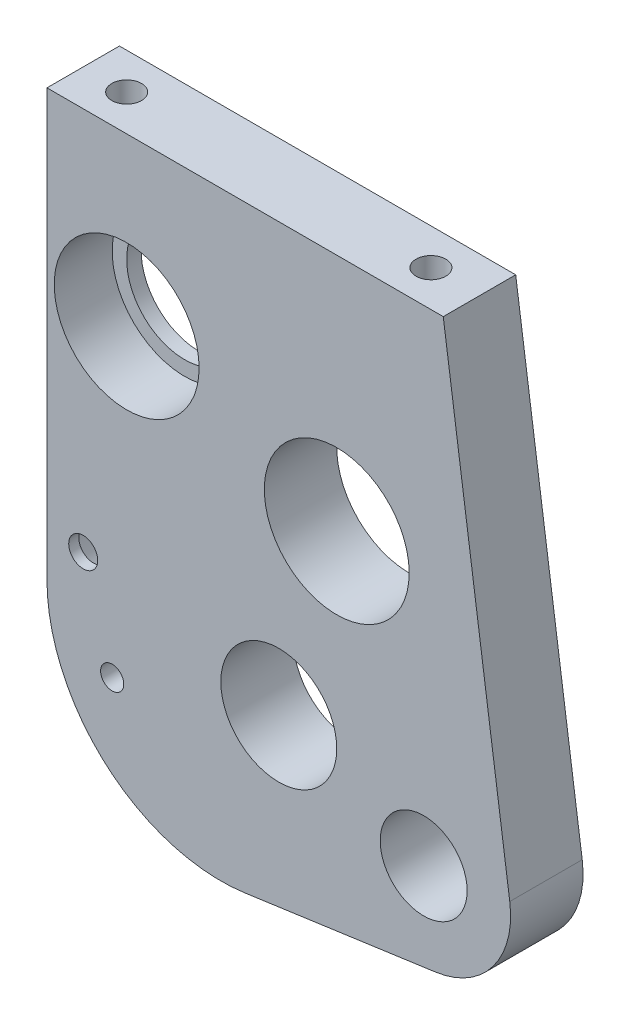
SolidWorks part; units mm, degrees
material "45"
ref_plane "前视基准面" through (0, 0, 0) normal (0, 0, 1) x (1, 0, 0)
ref_plane "上视基准面" through (0, 0, 0) normal (0, 1, 0) x (1, 0, 0)
ref_plane "右视基准面" through (0, 0, 0) normal (1, 0, 0) x (0, 0, -1)
sketch "草图1" plane through (0, 0, 0) normal (0, 0, 1) x (1, 0, 0)
  line L1 (0, 0) -> (34, 0)
  line L2 (0, 0) -> (0, -38.5)
  line L3 (0, -38.5) -> (34, -38.5)
  line L4 (34, 0) -> (34, -38.5)
  dimension "D1" = 34
  dimension "D2" = 38.5
  dimension "D3" = 90
extrude "拉伸1" add sketch "草图1" along normal blind 5
fillet "圆角1" radius 12 1 edges at (0, -38.5, 2.5)
sketch "草图2" plane through (0, 0, 5) normal (0, 0, 1) x (1, 0, 0)
  line L0 (0, 0) -> (0, -26.5) construction
  line L1 (34, 0) -> (0, 0) construction
  circle A0 centre (26, -32.5) radius 3
  dimension "D2" = 32.5
  dimension "D3" = 6
  dimension "D1" = 26
extrude "拉伸2" cut sketch "草图2" against normal up to surface (5 mm away) up to face at (15.5029, -21.1971, 0)
sketch "草图3" plane through (0, 0, 5) normal (0, 0, 1) x (1, 0, 0)
  line L0 (0, 0) -> (0, -26.5) construction
  line L1 (34, 0) -> (0, 0) construction
  circle A0 centre (5.5, -10.5) radius 4
  dimension "D1" = 5.5
  dimension "D2" = 10.5
  dimension "D3" = 8
extrude "拉伸3" cut sketch "草图3" against normal up to surface (5 mm away) up to face at (29, -32.5, 0)
sketch "草图4" plane through (0, 0, 5) normal (0, 0, 1) x (1, 0, 0)
  circle A0 centre (5.5, -10.5) radius 5
  dimension "D1" = 10
extrude "拉伸4" cut sketch "草图4" against normal blind 4
sketch "草图5" plane through (0, 0, 0) normal (0, 1, 0) x (1, 0, 0)
  line L0 (3, -2.5) -> (24, -2.5)
  line L1 (34, 0) -> (0, 0) construction
  line L2 (17, 0) -> (17, -2.5) construction
  line L3 (0, -5) -> (0, 0) construction
  dimension "D1" = 2.5
  dimension "D2" = 21
  dimension "D3" = 3
hole_wizard "M2.5 螺纹孔1" positions "3D草图1" profile "草图6" tap size "M2.5" standard "GB"
sketch3d "3D草图1"
  point P0 (3, 0, 2.5)
  point P3 (24, 0, 2.5)
sketch "草图6" plane through (3, 0, 2.5) normal (1, 0, 0) x (0, 0, 1)
  line L0 (0, 0) -> (0, 7.9659)
  line L1 (0, 7.9659) -> (1.025, 7.35)
  line L2 (1.025, 7.35) -> (1.025, 0)
  line L5 (1.025, 0) -> (0, 0)
  line L10 (0, 7.9659) -> (-1.025, 7.35) construction
  line L11 (0, -6.35) -> (0, 107.95) construction
  dimension "螺纹孔钻头直径" = 2.05
  dimension "螺纹孔钻头深度" = 7.35
  dimension "导头角度" = 118
cosmetic thread "孔螺蚊线1" parameters "D1"=6, "D2"=2.5
cosmetic thread "孔螺蚊线2" parameters "D1"=6, "D2"=2.5
chamfer "倒角1" [suppressed] distance 0.5 angle 45
chamfer "倒角2" [suppressed] distance 0.5 angle 45
sketch "草图7" plane through (0, 0, 0) normal (0, 0, -1) x (-1, 0, 0)
  line L1 (-12, -38.5) -> (-34, -38.5) construction
  line L2 (-31.9416, -31.665) -> (-27.4914, 0)
  line L3 (-34, 0) -> (0, 0) construction
  line L4 (-26, -38.5) -> (-34, -38.5)
  line L5 (-34, -38.5) -> (-34, 0) construction
  line L6 (-34, -38.5) -> (-34, 0)
  line L7 (-34, 0) -> (-27.4914, 0)
  arc A0 (-31.9416, -31.665) -> (-26, -38.5) centre (-26, -32.5) ccw
  circle A1 centre (-26, -32.5) radius 3 construction
  dimension "D1" = 6
  dimension "D2" = 8
extrude "拉伸5" cut sketch "草图7" against normal up to surface (5 mm away) up to face at (10.5, -10.5, 5)
sketch "Sketch1" plane through (0, 0, 0) normal (0, 0, -1) x (-1, 0, 0)
  line L0 (-26.835, -38.4416) -> (-13.6701, -40.2918)
  line L1 (0, 0) -> (0, -26.5) construction
  line L2 (0, -25.5198) -> (0, -28.4086)
  line L3 (-29.4415, -37.4149) -> (0, -25.5198)
  line L4 (-26, -32.5) -> (-29.4415, -37.4149) construction
  line L5 (-12, -38.5) -> (-26, -38.5) construction
  arc A0 (-31.9416, -31.665) -> (-26, -38.5) centre (-26, -32.5) ccw construction
  arc A1 (-29.4415, -37.4149) -> (-26.835, -38.4416) centre (-26, -32.5) ccw
  arc A3 (0, -28.4086) -> (-13.6701, -40.2918) centre (-12, -28.4086) cw
  dimension "D1" = 12
  dimension "D2" = 55
  dimension "D3" = 22
  dimension "D4" = 8
extrude "Extrude1" add sketch "Sketch1" against normal up to surface (5 mm away) up to face at (16.0842, -23.1674, 5)
sketch "草图8" plane through (0, 0, 0) normal (0, 0, -1) x (-1, 0, 0)
  line L1 (0, 0) -> (0, -28.4086) construction
  line L2 (-27.4914, 0) -> (0, 0) construction
  circle A0 centre (-2.5, -25.5) radius 1
  dimension "D3" = 2
  dimension "D1" = 25.5
  dimension "D2" = 2.5
extrude "拉伸6" cut sketch "草图8" against normal up to surface (5 mm away) up to face at (16.439, -23.8299, 5)
sketch "草图9" plane through (0, 0, 0) normal (0, 0, -1) x (-1, 0, 0)
  line L0 (-1.9, -29.2) -> (-6.1, -29.2)
  line L1 (-0.9, -28.2) -> (-0.9, -21)
  line L2 (-7.1, -28.2) -> (-7.1, -21)
  line L3 (-1.9, -20) -> (-6.1, -20)
  line L4 (-2.5, -25.5) -> (-7.596, -25.5) construction
  line L5 (-2.5, -25.5) -> (-2.5, -23.308) construction
  line L6 (-4, -20.9273) -> (-4, -31.0273) construction
  line L7 (0, 0) -> (0, -28.4086) construction
  line L8 (-4, -25.5) -> (-4, -20) construction
  arc A0 (-0.9, -28.2) -> (-1.9, -29.2) centre (-1.9, -28.2) cw
  arc A1 (-1.9, -20) -> (-0.9, -21) centre (-1.9, -21) cw
  arc A2 (-7.1, -21) -> (-6.1, -20) centre (-6.1, -21) cw
  arc A3 (-6.1, -29.2) -> (-7.1, -28.2) centre (-6.1, -28.2) cw
  point P10 (-4, -25.5)
  point P19 (-0.9, -20)
  point P22 (-7.1, -20)
  point P25 (-7.1, -29.2)
  dimension "D6" = 1
  dimension "D1" = 1.5
  dimension "D2" = 5.5
  dimension "D3" = 9.2
  dimension "D4" = 6.2
  dimension "D5" = 0
extrude "拉伸7" cut sketch "草图9" against normal blind 2.5
sketch "草图10" plane through (0, 0, 2.5) normal (0, 0, -1) x (-1, 0, 0)
  circle A0 centre (-4, -25.5) radius 3
  dimension "D1" = 6
extrude "拉伸8" cut sketch "草图10" against normal blind 1.8
sketch "草图11" plane through (0, 0, 5) normal (0, 0, -1) x (-1, 0, 0)
  line L0 (-4, -25.5) -> (-4, -32.5) construction
  line L1 (-4, -25.5) -> (-9.5, -25.5) construction
  line L2 (-4, -27.5) -> (-9.5, -27.5)
  dimension "D1" = 7
  dimension "D2" = 5.5
  dimension "D3" = 5.5
  dimension "D4" = 2
hole_wizard "M2.5 Tapped Hole2" [suppressed] positions "3D草图2" profile "草图12" tap size "M2.5" standard "GB"
sketch3d "3D草图2"
  point P0 (9.5, -25.5, 5)
  point P3 (4, -31.5, 5)
sketch "草图12" plane through (9.5, -25.5, 5) normal (1, 0, 0) x (0, -1, 0)
  line L0 (0, 0) -> (0, 6.9659)
  line L1 (0, 6.9659) -> (1.025, 6.35)
  line L2 (1.025, 6.35) -> (1.025, 0)
  line L5 (1.025, 0) -> (0, 0)
  line L10 (0, 6.9659) -> (-1.025, 6.35) construction
  line L11 (0, -6.35) -> (0, 107.95) construction
  dimension "Tap Drill Dia." = 2.05
  dimension "Tap Drill Depth" = 6.35
  dimension "Drill Angle" = 118
cosmetic thread "Hole Thread5" [suppressed] parameters "D1"=5, "D2"=2.5
cosmetic thread "Hole Thread6" [suppressed] parameters "D1"=5, "D2"=2.5
chamfer "倒角3" [suppressed] distance 0.2 angle 45
sketch "草图13" plane through (0, 0, 5) normal (0, 0, 1) x (1, 0, 0)
  line L0 (0, 0) -> (0, -28.4086) construction
  line L1 (27.4914, 0) -> (0, 0) construction
  circle A0 centre (20, -15.5) radius 5
  dimension "D1" = 10
  dimension "D3" = 15.5
  dimension "D2" = 20
extrude "拉伸9" cut sketch "草图13" against normal up to surface (5 mm away) up to face at (4, -24.6, 0)
sketch "草图15" plane through (0, 0, 0) normal (0, 0, -1) x (-1, 0, 0)
  line L1 (0, 0) -> (0, -28.4086) construction
  line L2 (-27.4914, 0) -> (0, 0) construction
  circle A0 centre (-16, -28.5) radius 4
  dimension "D1" = 8
  dimension "D3" = 16
  dimension "D2" = 28.5
extrude "拉伸10" cut sketch "草图15" against normal blind 10
sketch "Sketch7" plane through (0, 0, 0) normal (0, 0, -1) x (-1, 0, 0)
  line L0 (-27.4914, 0) -> (-27.3508, 1)
  line L1 (0, 0) -> (-27.4914, 0)
  line L2 (0, 0) -> (0, 1)
  line L3 (0, 1) -> (-27.3508, 1)
  line L5 (-31.9416, -31.665) -> (-27.4914, 0) construction
  dimension "D1" = 1
extrude "Extrude2" add sketch "Sketch7" against normal up to surface (5 mm away) up to face at (20, -28.5, 5)
sketch "Sketch8" plane through (0, 1, 0) normal (0, 1, 0) x (-1, 0, 0)
  circle A0 centre (-3, 2.5) radius 1.025
  circle A1 centre (-24, 2.5) radius 1.025
  dimension "D1" = 2.05
extrude "Extrude3" cut sketch "Sketch8" against normal blind 1
sketch "草图18" plane through (0, 0, 0) normal (0, 0, -1) x (-1, 0, 0)
  line L0 (-4.5, -25.5) -> (-4.5, -32) construction
  line L1 (-4.5, -25.5) -> (-4, -25.5) construction
  dimension "D1" = 6.5
  dimension "D2" = 0.5
hole_wizard "M2 螺纹孔1" positions "3D草图4" profile "草图19" tap size "M2" standard "GB" end condition through all
sketch3d "3D草图4"
  point P0 (4.5, -32, 0)
sketch "草图19" plane through (4.5, -32, 0) normal (1, 0, 0) x (0, 1, 0)
  line L0 (0, 0) -> (0, 5)
  line L1 (0, 5) -> (0.8, 5)
  line L2 (0.8, 5) -> (0.8, 0)
  line L5 (0.8, 0) -> (0, 0)
  line L11 (0, -6.35) -> (0, 107.95) construction
  dimension "通孔螺纹孔钻头直径" = 1.6
  dimension "通孔螺纹孔钻头深度" = 5
cosmetic thread "孔螺蚊线3" parameters "D2"=2
